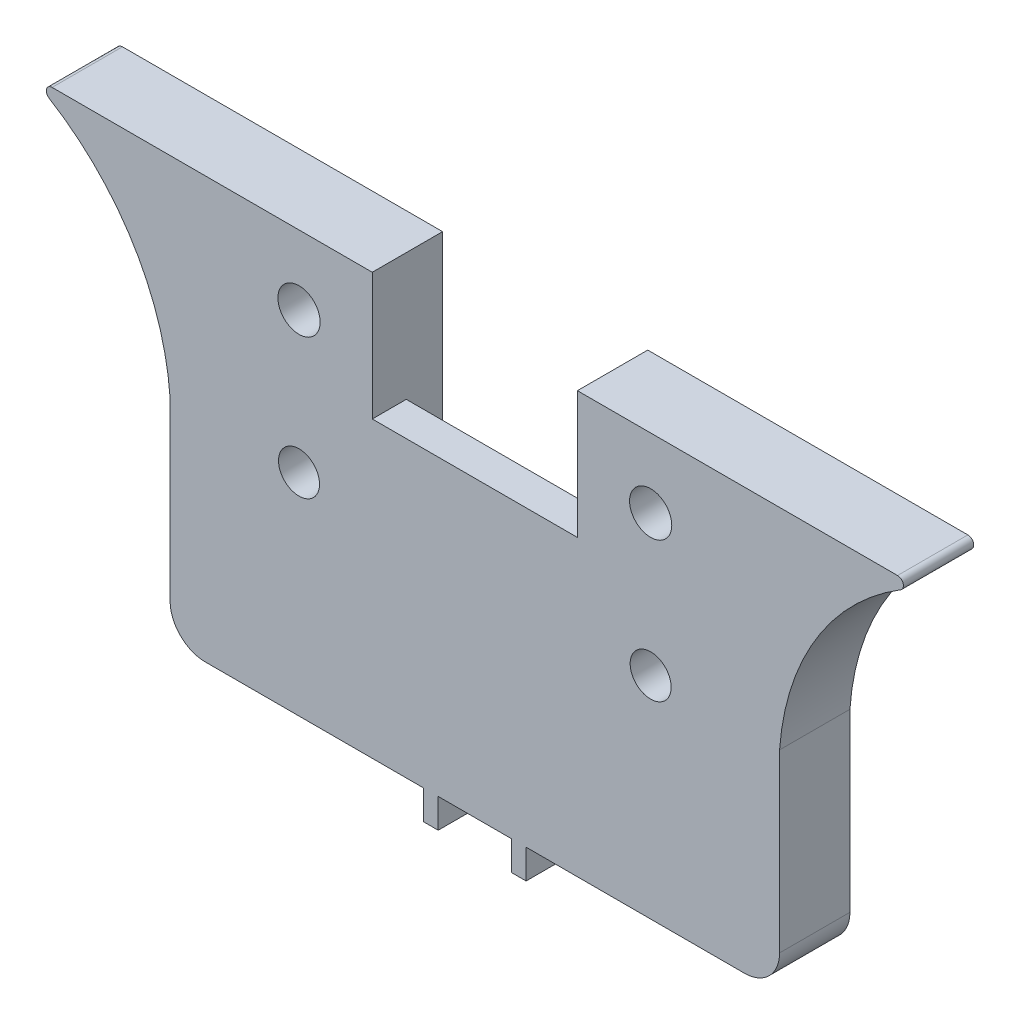
SolidWorks part; units mm, degrees
ref_plane "Front Plane" through (0, 0, 0) normal (0, 0, 1) x (1, 0, 0)
ref_plane "Top Plane" through (0, 0, 0) normal (0, 1, 0) x (1, 0, 0)
ref_plane "Right Plane" through (0, 0, 0) normal (1, 0, 0) x (0, 0, -1)
sketch "Sketch2" plane through (0, 0, 0) normal (0, 0, 1) x (1, 0, 0)
  line L0 (0, -33.2846) -> (0, 67.9981) construction
  line L12 (45.8007, 37.8996) -> (-45.8007, 37.8996)
  line L13 (-33.02, 15.1445) -> (-33.02, -3.9055)
  line L14 (-29.21, -7.7155) -> (29.21, -7.7155)
  line L15 (33.02, 15.1445) -> (33.02, -3.9055)
  circle A4 centre (-19.05, 15.1445) radius 2.2225
  circle A12 centre (19.05, 15.1445) radius 2.2225
  arc A13 (-33.02, 15.1445) -> (-46.1321, 36.723) centre (-60.5269, 13.203) ccw
  arc A14 (33.02, 15.1445) -> (46.1321, 36.723) centre (60.5269, 13.203) cw
  arc A15 (33.02, -3.9055) -> (29.21, -7.7155) centre (29.21, -3.9055) cw
  arc A16 (-33.02, -3.9055) -> (-29.21, -7.7155) centre (-29.21, -3.9055) ccw
  arc A17 (46.1321, 36.723) -> (45.8007, 37.8996) centre (45.8007, 37.2646) ccw
  arc A18 (-45.8007, 37.8996) -> (-46.1321, 36.723) centre (-45.8007, 37.2646) ccw
  point P4 (0, 57.6776)
  point P9 (0, 19.5776)
  point P12 (0, 37.8996)
  point P16 (0, -7.7155)
  point P18 (33.02, -7.7155)
  point P20 (0, -3.9055)
  point P22 (-33.02, -7.7155)
  point P27 (48.26, 37.8996)
  point P30 (-48.26, 37.8996)
  dimension "D2" = 48.26
  dimension "D3" = 22.86
  dimension "D6" = 0.635
  dimension "D4" = 33.02
  dimension "D5" = 3.81
  dimension "D7" = 27.5753
  dimension "D8" = 19.05
  dimension "D9" = 45.8007
  dimension "D10" = 19.05
  dimension "D11" = 19.5776
  dimension "D12" = 57.6776
  dimension "D1" = 4.445
extrude "Boss-Extrude1" add sketch "Sketch2" along normal blind 7.62
sketch "Sketch11" plane through (0, 0, 7.62) normal (0, 0, 1) x (1, 0, 0)
  line L0 (0, 41.9648) -> (0, -47.1588) construction
  line L1 (-19.05, 15.1445) -> (-19.05, 30.3845) construction
  circle A0 centre (-19.05, 30.3845) radius 2.286
  circle A1 centre (19.05, 30.3845) radius 2.286
  dimension "D2" = 4.572
  dimension "D1" = 15.24
extrude "Cut-Extrude9" cut sketch "Sketch11" against normal through all
sketch "Sketch12" plane through (0, 0, 0) normal (0, 0, 1) x (1, 0, 0)
  line L0 (0, 39.594) -> (0, -43.4023) construction
  line L1 (-4.7625, 33.4498) -> (4.7625, 33.4498)
  line L3 (4.7625, 10.9708) -> (-4.7625, 10.9708)
  line L4 (-11.1125, 17.3208) -> (-11.1125, 27.0998)
  line L5 (11.1125, 17.3208) -> (11.1125, 27.0998)
  arc A0 (11.1125, 27.0998) -> (4.7625, 33.4498) centre (4.7625, 27.0998) ccw
  arc A1 (11.1125, 17.3208) -> (4.7625, 10.9708) centre (4.7625, 17.3208) cw
  arc A2 (-4.7625, 10.9708) -> (-11.1125, 17.3208) centre (-4.7625, 17.3208) cw
  arc A3 (-4.7625, 33.4498) -> (-11.1125, 27.0998) centre (-4.7625, 27.0998) ccw
  point P10 (0, 10.9708)
  point P11 (0, 33.4498)
  point P13 (11.1125, 33.4498)
  point P16 (11.1125, 10.9708)
  point P19 (-11.1125, 10.9708)
  point P22 (-11.1125, 33.4498)
  dimension "D4" = 6.35
  dimension "D1" = 11.1125
  dimension "D2" = 10.9708
  dimension "D3" = 22.479
extrude "Cut-Extrude11" cut sketch "Sketch12" along normal blind 3.937
sketch "Sketch13" plane through (0, 0, 0) normal (0, 0, -1) x (-1, 0, 0)
  line L2 (-11.1125, 40.3062) -> (-11.1125, 24.1288)
  line L3 (-11.1125, 24.1288) -> (11.1125, 24.1288)
  line L7 (-11.1125, 40.3062) -> (11.1125, 40.3062)
  line L8 (11.1125, 40.3062) -> (11.1125, 24.1288)
  point P3 (0, 0)
  point P4 (0, 0)
  dimension "D1" = 11.1125
  dimension "D2" = 11.1125
  dimension "D3" = 24.1288
  dimension "D4" = 40.3062
extrude "Cut-Extrude12" cut sketch "Sketch13" against normal through all
sketch "Sketch15" plane through (0, -7.7155, 0) normal (0, -1, 0) x (1, 0, 0)
  line L0 (0, -11.1019) -> (0, 17.7532) construction
  line L1 (-29.21, 3.81) -> (29.21, 3.81) construction
  line L4 (-29.21, 7.62) -> (-29.21, 0) construction
  line L5 (29.21, 7.62) -> (29.21, 0) construction
  circle A0 centre (0, 3.81) radius 2.032
  dimension "D1" = 4.064
extrude "Cut-Extrude14" cut sketch "Sketch15" against normal blind 17.78
sketch "Sketch16" plane through (0, 0, 0) normal (0, 0, -1) x (-1, 0, 0)
  line L0 (29.21, -7.7155) -> (-29.21, -7.7155) construction
  line L1 (-3.9687, -7.7155) -> (-5.5563, -7.7155)
  line L2 (-3.9687, -7.7155) -> (-3.9688, -10.8905)
  line L3 (-3.9688, -10.8905) -> (-5.5563, -10.8905)
  line L4 (-5.5563, -7.7155) -> (-5.5563, -10.8905)
  line L5 (0, -11.3212) -> (0, 10.1435) construction
  line L6 (5.5562, -7.7155) -> (3.9688, -7.7155)
  line L7 (5.5562, -7.7155) -> (5.5562, -10.8905)
  line L8 (5.5562, -10.8905) -> (3.9688, -10.8905)
  line L9 (3.9688, -7.7155) -> (3.9688, -10.8905)
  dimension "D1" = 1.5875
  dimension "D2" = 3.175
  dimension "D3" = 7.9375
  dimension "D4" = 3.9688
extrude "Boss-Extrude2" add sketch "Sketch16" against normal up to surface (7.62 mm away) up to face at (-16.764, 30.3845, 7.62)
equation "\"D4@Sketch16\"=\"D3@Sketch16\"/2"
